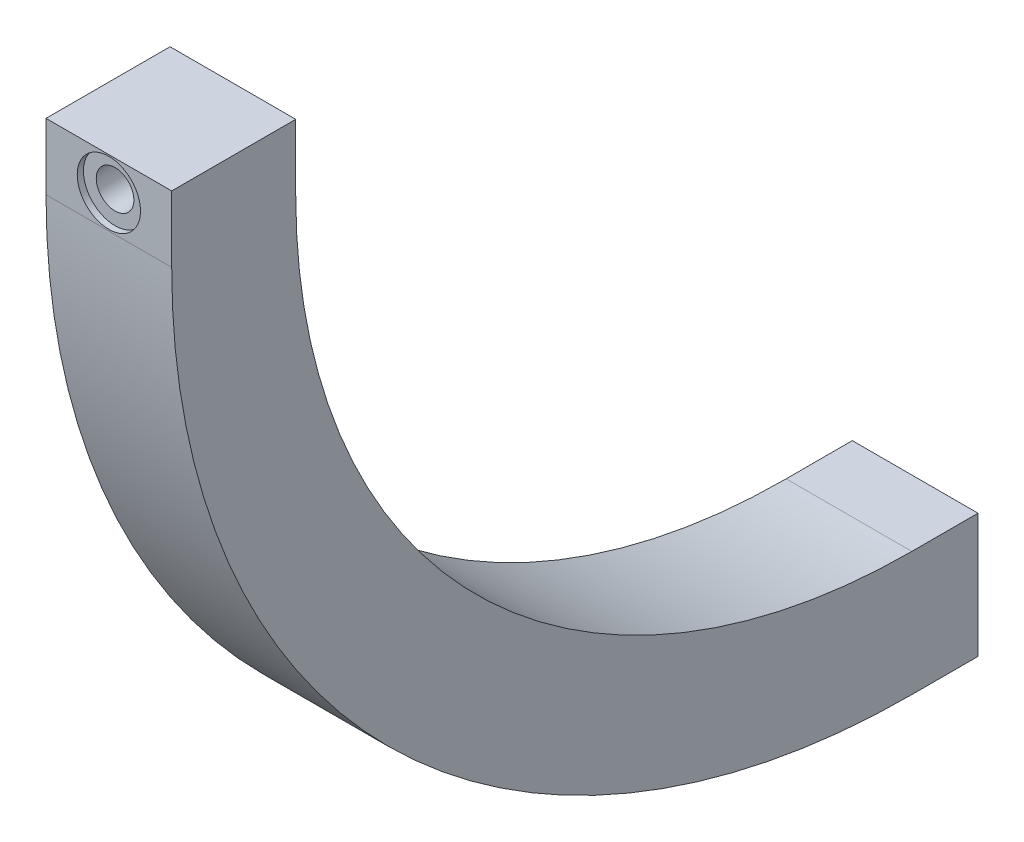
SolidWorks part; units mm, degrees
ref_plane "Front Plane" through (0, 0, 0) normal (0, 0, 1) x (1, 0, 0)
ref_plane "Top Plane" through (0, 0, 0) normal (0, 1, 0) x (1, 0, 0)
ref_plane "Right Plane" through (0, 0, 0) normal (1, 0, 0) x (0, 0, -1)
ref_axis "Z" through (0, 0, 22.75) along (0, 0, -1)
sketch "Sketch4" plane through (0, 0, 0) normal (0, 0, 1) x (1, 0, 0)
  circle A0 centre (0, 0) radius 77.5 construction
  dimension "D1" = 155
sketch "Sketch5" plane through (0, 0, 0) normal (1, 0, 0) x (0, 0, -1)
  line L0 (-78.5, 4) -> (-78.5, 0)
  line L1 (-78.5, 0) -> (-78.5, -4)
  line L2 (-93.5, -4) -> (-93.5, 4)
  line L6 (-93.5, 4) -> (-78.5, 4)
  line L12 (-22.75, 0) -> (-13.0351, 0) construction
  line L13 (0, 0) -> (-14.9091, -14.9091) construction
  line L14 (0, 0) -> (7.0065, 0) construction
  line L15 (0, -78.5) -> (-4, -78.5)
  line L16 (4, -78.5) -> (0, -78.5)
  line L17 (-4, -93.5) -> (4, -93.5)
  line L18 (4, -93.5) -> (4, -78.5)
  circle A0 centre (0, 0) radius 14 construction
  arc A1 (-78.5, -4) -> (-4, -78.5) centre (-4, -4) ccw
  arc A2 (-93.5, -4) -> (-4, -93.5) centre (-4, -4) ccw
  point P2 (9.4307, -21)
  point P4 (0, -2.1363)
  dimension "D1" = 28
  dimension "D4" = 4
  dimension "D2" = 45
  dimension "D3" = 15
  dimension "D5" = 78.5
sketch "Sketch6" plane through (0, 0, 0) normal (0, 1, 0) x (1, 0, 0)
  circle A0 centre (0, 0) radius 77.5 construction
  dimension "D1" = 155
extrude "Boss-Extrude1" add sketch "Sketch5" along normal blind 7.6 and the other way blind 7.6
sketch "Sketch7" plane through (0, 0, 0) normal (0, 0, 1) x (1, 0, 0)
  circle A0 centre (0, 0) radius 1.75
  dimension "D1" = 3.5
extrude "Cut-Extrude1" cut sketch "Sketch7" along normal through all
ref_axis "Y" through (0, -9.3489, 0) along (0, -1, 0)
sketch "Sketch12" plane through (0, 0, 93.5) normal (0, 0, 1) x (1, 0, 0)
  circle A0 centre (0, 0) radius 2.275
  dimension "D1" = 4.55
extrude "Cut-Extrude7" cut sketch "Sketch12" against normal blind 6
sketch "Sketch14" plane through (0, 0, 93.5) normal (0, 0, -1) x (1, 0, 0)
  circle A0 centre (0, 0) radius 3.825
  dimension "D1" = 7.65
extrude "Cut-Extrude10" cut sketch "Sketch14" along normal blind 0.75
sketch "Sketch16" plane through (0, 0, 0) normal (1, 0, 0) x (0, 0, -1)
  line L0 (0, -94.5) -> (0, 0) construction
  dimension "D1" = 94.5
ref_plane "Plane1" through (0, -94.5, 0) normal (0, 1, 0) x (1, 0, 0)
ref_axis "CX" through (0, -94.5, 4.4) along (0, 0, -1)
ref_plane "Plane2" through (0, 0, 0) normal (0, 0, -1) x (0, 1, 0)
ref_plane "Plane3" through (0, 0, 0) normal (1, 0, 0) x (0, 0, -1)
ref_axis "CZ" through (0, -8.7018, 0) along (0, -1, 0)
ref_axis "CY" through (-0.6471, -94.5, 0) along (1, 0, 0)
ref_point "CO"
sketch "Sketch15" plane through (0, -93.5, 0) normal (0, -1, 0) x (1, 0, 0)
  circle A0 centre (0, 0) radius 1.5
  dimension "D1" = 3
extrude "Cut-Extrude11" cut sketch "Sketch15" against normal blind 6
equation "\"rbracket-width\"= \"L2Thickness\" + 0.2"
equation "\"EyeCaptureRadius\"= ( \"EyeDiameter\" + \"EyeClearance\" ) / 2"
equation "\"rbracket_planetocenterline_dist\"= \"BasePlaneDistance\""
equation "\"EyeDiameter\" = 155"
equation "\"BasePlaneDistance\" = \"EyeDiameter\"/2+\"L2Thickness\"+\"EyeClearance\""
equation "\"EyeClearance\" = 2"
equation "\"D1@Sketch4\"=\"EyeDiameter\""
equation "\"D1@Sketch6\"=\"EyeDiameter\""
equation "\"D1@Boss-Extrude1\"=\"rbracket-width\"/2"
equation "\"D2@Boss-Extrude1\"=\"rbracket-width\"/2"
equation "\"L2Thickness\" = 15"
equation "\"D3@Sketch5\"=\"L2Thickness\""
equation "\"D5@Sketch5\"=(\"EyeDiameter\"+\"EyeClearance\")/2"
equation "\"BearingThickness\"= 6"
equation "\"BearingOD\"=4.5"
equation "\"OuterBearingProudDistance\"= 0"
equation "\"D1@Cut-Extrude7\"=\"BearingThickness\"-\"OuterBearingProudDistance\""
equation "\"D1@Sketch12\"= \"BearingOD\" + \"PrinterFilamentThickness\" *\"ApplyPrinterOffset\" / 2"
equation "\"FlangeOD\"=7.5"
equation "\"FlangeThickness\"= 0.75"
equation "\"D1@Sketch14\"=\"FlangeOD\" + \"PrinterFilamentThickness\"*1.5 * \"ApplyPrinterOffset\""
equation "\"D1@Cut-Extrude10\"=\"FlangeThickness\""
equation "\"PrinterFilamentThickness\"= 0.1'For setting distances for things like pressfits"
equation "\"ApplyPrinterOffset\"= 1'Set to 0 for line-to-line. Set to 1 for applying guestimate dimensions to make the printer produce good parts"
equation "\"D1@Cut-Extrude11\"=3*1.5"
equation "\"D1@Sketch16\"=\"BasePlaneDistance\""
